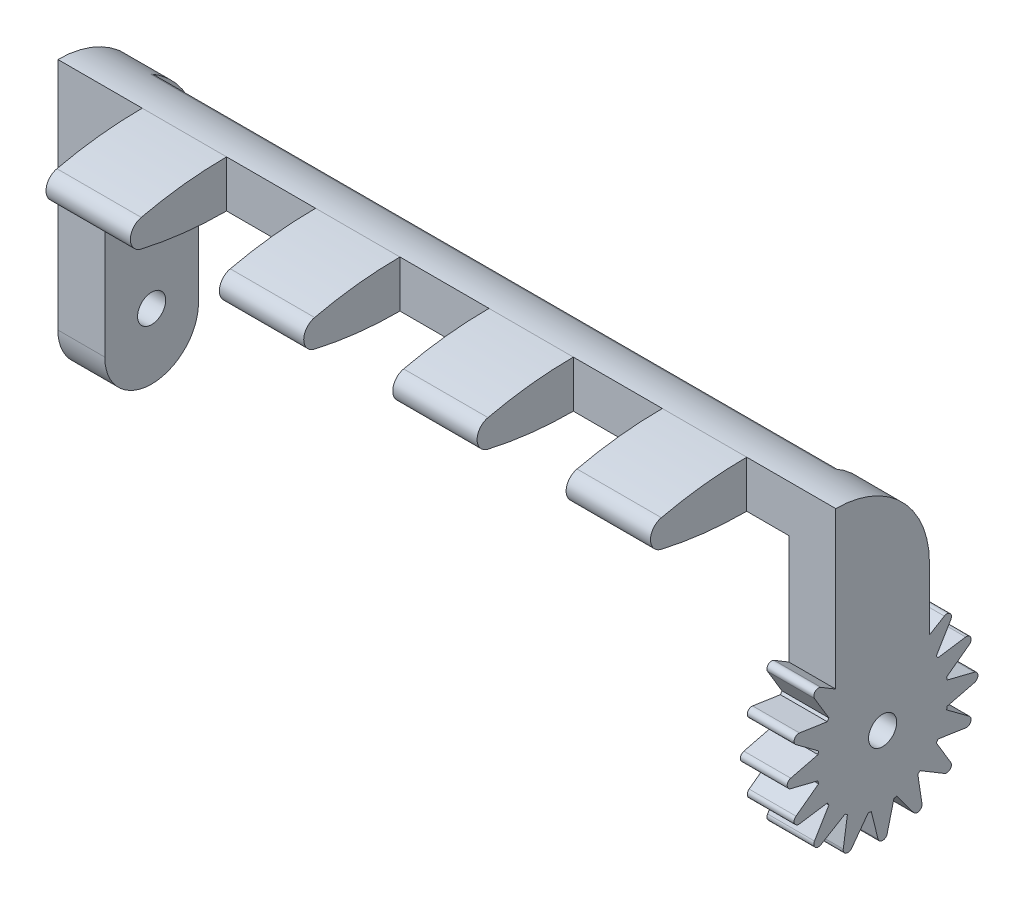
SolidWorks part; units mm, degrees
ref_plane "Plan de face" through (0, 0, 0) normal (0, 0, 1) x (1, 0, 0)
ref_plane "Plan de dessus" through (0, 0, 0) normal (0, 1, 0) x (1, 0, 0)
ref_plane "Plan de droite" through (0, 0, 0) normal (1, 0, 0) x (0, 0, -1)
sketch "Esquisse1" plane through (0, 0, 0) normal (0, 0, 1) x (1, 0, 0)
  line L0 (-36.5, 10) -> (36.5, 10)
  line L1 (-41.5, 15) -> (41.5, 15)
  line L2 (-41.5, 15) -> (-41.5, -15)
  line L3 (-41.5, -15) -> (-36.5, -15)
  line L4 (41.5, 15) -> (41.5, -15)
  line L5 (-41.5, 15) -> (41.5, -15) construction
  line L6 (-41.5, -15) -> (41.5, 15) construction
  line L7 (36.5, 10) -> (36.5, -10)
  line L8 (-36.5, -10) -> (36.5, -10) construction
  line L9 (-36.5, 10) -> (-36.5, -10)
  line L10 (-36.5, -10) -> (-36.5, -15)
  line L11 (36.5, -10) -> (36.5, -15)
  line L12 (36.5, -15) -> (41.5, -15)
  line L13 (-41.5, -15) -> (41.5, -15) construction
  point P0 (0, 0)
  dimension "D1" = 83
  dimension "D2" = 30
  dimension "D3" = 5
extrude "Boss.-Extru.1" add sketch "Esquisse1" along normal blind 10
sketch "Esquisse2" plane through (-41.5, 0, 0) normal (-1, 0, 0) x (0, 0, 1)
  line L0 (10, 15) -> (0, 15) construction
  line L1 (10, 15) -> (10, -15) construction
  line L2 (24, 12.5) -> (10, 12.5) construction
  line L3 (10, 10) -> (10, 15)
  line L4 (10, 10) -> (0, 10) construction
  line L5 (10, 10) -> (0, 10) construction
  arc A0 (10, 15) -> (24, 12.5) centre (10, -25.45) cw
  arc A1 (10, 10) -> (24, 12.5) centre (10, 50.45) ccw
  dimension "D2" = 14
extrude "Boss.-Extru.2" add sketch "Esquisse2" against normal blind 9 from offset 9 offset against normal yes
fillet "Congé1" radius 1.5 1 edges at (-28, 12.5, 24)
pattern_linear "Répétition linéaire1" count 4 spacing 18.5 along (1, 0, 0) of "Boss.-Extru.2", "Congé1"
sketch "Esquisse4" plane through (-36.5, 0, 0) normal (1, 0, 0) x (0, 0, -1)
  line L0 (-10, -8) -> (0, -8) construction
  line L4 (0, -15) -> (0, 10)
  line L5 (0, 10) -> (-10, 10)
  line L6 (-10, 10) -> (-10, -15)
  line L7 (-10, -15) -> (0, -15)
  line L8 (0, -15) -> (0, 10)
  line L9 (0, 10) -> (-10, 10)
  line L10 (-10, 10) -> (-10, -15) construction
  line L11 (-10, -15) -> (0, -15)
  circle A0 centre (-5, -8) radius 1.5
  dimension "D3" = 3
  dimension "D2" = 7
  dimension "D1" = 0
extrude "Enlèv. mat.-Extru.1" cut sketch "Esquisse4" against normal through all and the other way through all contours A0 region at (-36.5, -8, 5)
fillet "Congé2" 2 edges at (-39, -15, 0) (-39, -15, 10) type full round first side face at (0, -1.25, 0) second side face at (-36.8333, 3.3333, 10) middle face at (-39, -15, 5)
fillet "Congé3" 2 edges at (39, -15, 0) (39, -15, 10) type full round first side face at (0, 0, 0) second side face at (36.6667, 3.3333, 10) middle face at (39, -15, 5)
fillet "Congé4" radius 10 1 edges at (0, 15, 0)
sketch "Esquisse5" plane through (-36.5, 0, 0) normal (1, 0, 0) x (0, 0, -1)
  line L0 (-12, -8) -> (2, -8) construction
  line L1 (-14.8004, -8.4851) -> (-11.8947, -9.2096)
  line L2 (-14.8004, -7.5149) -> (-11.8947, -6.7904)
  line L3 (-14.24, -4.6978) -> (-11.8328, -6.479)
  line L4 (-13.8687, -3.8013) -> (-10.907, -4.244)
  line L5 (-12.2729, -1.4132) -> (-10.7306, -3.98)
  line L6 (-11.5868, -0.7271) -> (-9.02, -2.2694)
  line L7 (-9.1987, 0.8687) -> (-8.756, -2.093)
  line L8 (-8.3022, 1.24) -> (-6.521, -1.1672)
  line L9 (-5.4851, 1.8004) -> (-6.2096, -1.1053)
  line L10 (-4.5149, 1.8004) -> (-3.7904, -1.1053)
  line L11 (-1.6978, 1.24) -> (-3.479, -1.1672)
  line L12 (-0.8013, 0.8687) -> (-1.244, -2.093)
  line L13 (1.5868, -0.7271) -> (-0.98, -2.2694)
  line L14 (2.2729, -1.4132) -> (0.7306, -3.98)
  line L15 (3.8687, -3.8013) -> (0.907, -4.244)
  line L16 (4.24, -4.6978) -> (1.8328, -6.479)
  line L17 (4.8004, -7.5149) -> (1.8947, -6.7904)
  line L18 (4.8004, -8.4851) -> (1.8947, -9.2096)
  line L19 (4.24, -11.3022) -> (1.8328, -9.521)
  line L20 (3.8687, -12.1987) -> (0.907, -11.756)
  line L21 (2.2729, -14.5868) -> (0.7306, -12.02)
  line L22 (1.5868, -15.2729) -> (-0.98, -13.7306)
  line L23 (-0.8013, -16.8687) -> (-1.244, -13.907)
  line L24 (-1.6978, -17.24) -> (-3.479, -14.8328)
  line L25 (-4.5149, -17.8004) -> (-3.7904, -14.8947)
  line L26 (-5.4851, -17.8004) -> (-6.2096, -14.8947)
  line L27 (-8.3022, -17.24) -> (-6.521, -14.8328)
  line L28 (-9.1987, -16.8687) -> (-8.756, -13.907)
  line L29 (-11.5868, -15.2729) -> (-9.02, -13.7306)
  line L30 (-12.2729, -14.5868) -> (-10.7306, -12.02)
  line L31 (-13.8687, -12.1987) -> (-10.907, -11.756)
  line L32 (-14.24, -11.3022) -> (-11.8328, -9.521)
  arc A0 (-10.907, -11.756) -> (-10.7306, -12.02) centre (-5, -8) ccw
  arc A1 (-10, -10) -> (0, -10) centre (-5, -10) ccw construction
  arc A2 (-14.8004, -8.4851) -> (-14.8004, -7.5149) centre (-14.6794, -8) cw
  arc A3 (-14.24, -4.6978) -> (-13.8687, -3.8013) centre (-13.9426, -4.2959) cw
  arc A4 (-12.2729, -1.4132) -> (-11.5868, -0.7271) centre (-11.8444, -1.1556) cw
  arc A5 (-9.1987, 0.8687) -> (-8.3022, 1.24) centre (-8.7041, 0.9426) cw
  arc A6 (-5.4851, 1.8004) -> (-4.5149, 1.8004) centre (-5, 1.6794) cw
  arc A7 (-1.6978, 1.24) -> (-0.8013, 0.8687) centre (-1.2959, 0.9426) cw
  arc A8 (1.5868, -0.7271) -> (2.2729, -1.4132) centre (1.8444, -1.1556) cw
  arc A9 (3.8687, -3.8013) -> (4.24, -4.6978) centre (3.9426, -4.2959) cw
  arc A10 (4.8004, -7.5149) -> (4.8004, -8.4851) centre (4.6794, -8) cw
  arc A11 (4.24, -11.3022) -> (3.8687, -12.1987) centre (3.9426, -11.7041) cw
  arc A12 (2.2729, -14.5868) -> (1.5868, -15.2729) centre (1.8444, -14.8444) cw
  arc A13 (-0.8013, -16.8687) -> (-1.6978, -17.24) centre (-1.2959, -16.9426) cw
  arc A14 (-4.5149, -17.8004) -> (-5.4851, -17.8004) centre (-5, -17.6794) cw
  arc A15 (-8.3022, -17.24) -> (-9.1987, -16.8687) centre (-8.7041, -16.9426) cw
  arc A16 (-11.5868, -15.2729) -> (-12.2729, -14.5868) centre (-11.8444, -14.8444) cw
  arc A17 (-13.8687, -12.1987) -> (-14.24, -11.3022) centre (-13.9426, -11.7041) cw
  arc A18 (-9.02, -13.7306) -> (-8.756, -13.907) centre (-5, -8) ccw
  arc A19 (-6.521, -14.8328) -> (-6.2096, -14.8947) centre (-5, -8) ccw
  arc A20 (-3.7904, -14.8947) -> (-3.479, -14.8328) centre (-5, -8) ccw
  arc A21 (-1.244, -13.907) -> (-0.98, -13.7306) centre (-5, -8) ccw
  arc A22 (0.7306, -12.02) -> (0.907, -11.756) centre (-5, -8) ccw
  arc A23 (1.8328, -9.521) -> (1.8947, -9.2096) centre (-5, -8) ccw
  arc A24 (1.8947, -6.7904) -> (1.8328, -6.479) centre (-5, -8) ccw
  arc A25 (0.907, -4.244) -> (0.7306, -3.98) centre (-5, -8) ccw
  arc A26 (-0.98, -2.2694) -> (-1.244, -2.093) centre (-5, -8) ccw
  arc A27 (-3.479, -1.1672) -> (-3.7904, -1.1053) centre (-5, -8) ccw
  arc A28 (-6.2096, -1.1053) -> (-6.521, -1.1672) centre (-5, -8) ccw
  arc A29 (-8.756, -2.093) -> (-9.02, -2.2694) centre (-5, -8) ccw
  arc A30 (-10.7306, -3.98) -> (-10.907, -4.244) centre (-5, -8) ccw
  arc A31 (-11.8328, -6.479) -> (-11.8947, -6.7904) centre (-5, -8) ccw
  arc A32 (-11.8947, -9.2096) -> (-11.8328, -9.521) centre (-5, -8) ccw
  circle A33 centre (-5, -8) radius 1.5 construction
  circle A34 centre (-5, -8) radius 1.5
  point P14 (-16.7462, -8)
  point P92 (-5, -8)
  dimension "D3" = 0.5
  dimension "D1" = 14
  dimension "D2" = 5
  dimension "D4" = 16
extrude "Boss.-Extru.3" add sketch "Esquisse5" along normal blind 5 from surface starting at face at (36.5, -8, 3.5)
fillet "Congé7" radius 2 1 edges at (0, 10, 1.3397)
